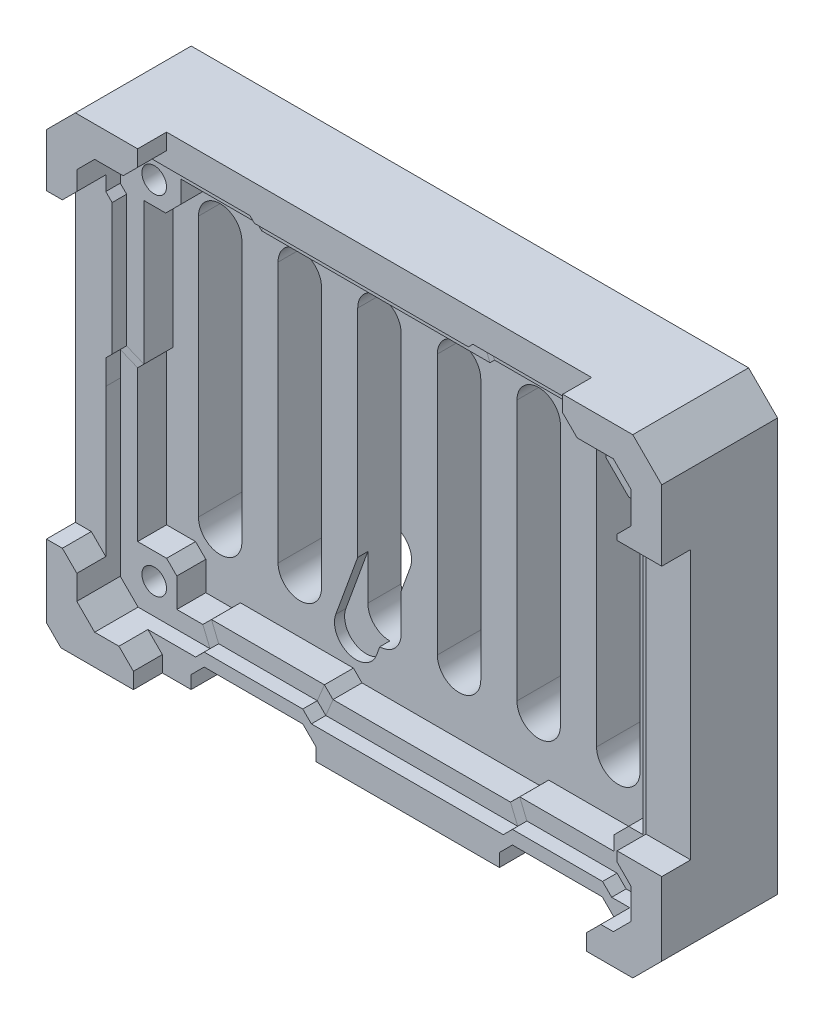
SolidWorks part; units mm, degrees
ref_plane "前视基准面" through (0, 0, 0) normal (0, 0, 1) x (1, 0, 0)
ref_plane "上视基准面" through (0, 0, 0) normal (0, 1, 0) x (1, 0, 0)
ref_plane "右视基准面" through (0, 0, 0) normal (1, 0, 0) x (0, 0, -1)
other "Configuration Table"
sketch "草图1" plane through (0, 0, 0) normal (0, 0, 1) x (1, 0, 0)
  line L1 (0, 0) -> (75, 0)
  line L2 (0, 0) -> (0, -55)
  line L3 (0, -55) -> (75, -55)
  line L4 (75, 0) -> (75, -55)
  dimension "D1" = 55
  dimension "D2" = 75
extrude "凸台-拉伸1" add sketch "草图1" along normal blind 12
sketch "草图2" plane through (0, 0, 0) normal (0, 0, -1) x (-1, 0, 0)
  circle A0 centre (-71.1669, -3.5575) radius 1.7
  circle A1 centre (-71.1669, -51.5849) radius 1.7
  circle A2 centre (-3.8888, -51.5849) radius 1.7
  circle A3 centre (-3.8888, -3.5575) radius 1.7
  dimension "D1" = 3.4
  dimension "D2" = 3.4
  dimension "D3" = 3.4
  dimension "D4" = 3.4
extrude "切除-拉伸1" cut sketch "草图2" against normal blind 12
sketch "草图3" plane through (0, 0, 0) normal (0, 0, -1) x (-1, 0, 0)
  line L1 (-73.9669, -0.7575) -> (-68.3669, -0.7575)
  line L2 (-73.9669, -0.7575) -> (-73.9669, -6.3575)
  line L3 (-73.9669, -6.3575) -> (-68.3669, -6.3575)
  line L4 (-68.3669, -0.7575) -> (-68.3669, -6.3575)
  line L5 (-73.9669, -0.7575) -> (-68.3669, -6.3575) construction
  line L6 (-73.9669, -6.3575) -> (-68.3669, -0.7575) construction
  line L11 (-6.6888, -0.7575) -> (-1.0888, -0.7575)
  line L12 (-6.6888, -0.7575) -> (-6.6888, -6.3575)
  line L13 (-6.6888, -6.3575) -> (-1.0888, -6.3575)
  line L14 (-1.0888, -0.7575) -> (-1.0888, -6.3575)
  line L15 (-6.6888, -0.7575) -> (-1.0888, -6.3575) construction
  line L16 (-6.6888, -6.3575) -> (-1.0888, -0.7575) construction
  line L17 (-73.9669, -48.7849) -> (-68.3669, -48.7849)
  line L18 (-73.9669, -48.7849) -> (-73.9669, -54.3849)
  line L19 (-73.9669, -54.3849) -> (-68.3669, -54.3849)
  line L20 (-68.3669, -48.7849) -> (-68.3669, -54.3849)
  line L21 (-73.9669, -48.7849) -> (-68.3669, -54.3849) construction
  line L22 (-73.9669, -54.3849) -> (-68.3669, -48.7849) construction
  line L23 (-6.6888, -48.7849) -> (-1.0888, -48.7849)
  line L24 (-6.6888, -48.7849) -> (-6.6888, -54.3849)
  line L25 (-6.6888, -54.3849) -> (-1.0888, -54.3849)
  line L26 (-1.0888, -48.7849) -> (-1.0888, -54.3849)
  line L27 (-6.6888, -48.7849) -> (-1.0888, -54.3849) construction
  line L28 (-6.6888, -54.3849) -> (-1.0888, -48.7849) construction
  circle A0 centre (-71.1669, -3.5575) radius 1.7 construction
  circle A1 centre (-3.8888, -3.5575) radius 1.7 construction
  circle A2 centre (-71.1669, -51.5849) radius 1.7 construction
  circle A3 centre (-3.8888, -51.5849) radius 1.7 construction
  point P0 (-71.1669, -3.5575)
  point P5 (0, 0)
  point P8 (-71.1669, -51.5849)
  point P12 (-3.8888, -3.5575)
  point P22 (-3.8888, -51.5849)
  dimension "D1" = 5.6
  dimension "D2" = 5.6
  dimension "D3" = 5.6
  dimension "D4" = 5.6
  dimension "D5" = 5.6
  dimension "D6" = 5.6
  dimension "D7" = 5.6
  dimension "D8" = 5.6
extrude "切除-拉伸2" cut sketch "草图3" along normal blind 2.5 from offset 4 offset against normal yes
sketch "草图5" plane through (0, 0, 0) normal (0, 0, -1) x (-1, 0, 0)
  line L1 (-80, 5) -> (5, 5)
  line L2 (-80, 5) -> (-80, -60)
  line L3 (-80, -60) -> (5, -60)
  line L4 (5, 5) -> (5, -60)
  line L5 (-80, 5) -> (5, -60) construction
  line L6 (-80, -60) -> (5, 5) construction
  line L10 (-75, 0) -> (0, 0) construction
  line L11 (0, 0) -> (0, -55) construction
  line L12 (-75, -55) -> (-75, 0) construction
  line L13 (-75, 0) -> (0, 0)
  line L14 (-75, 0) -> (-75, -55)
  line L15 (-75, -55) -> (0, -55)
  line L16 (0, 0) -> (0, -55)
  line L17 (0, -55) -> (-75, -55) construction
  point P0 (-37.5, -27.5)
  dimension "D1" = 65
  dimension "D2" = 85
  dimension "D3" = 5
  dimension "D4" = 5
extrude "凸台-拉伸2" add sketch "草图5" against normal up to surface (12 mm away) up to face at (2.1888, -3.5575, 12)
sketch "草图6" plane through (0, 0, 12) normal (0, 0, 1) x (1, 0, 0)
  line L56 (0.8713, -25.6658) -> (0, -26.5371)
  line L57 (0, -26.5371) -> (0, -53.0074)
  line L58 (0, -53.0074) -> (1.9926, -55)
  line L59 (1.9926, -55) -> (11.2697, -55)
  line L60 (11.2697, -55) -> (12.4616, -53.8134)
  line L61 (12.4616, -53.8134) -> (26.7436, -53.8171)
  line L62 (26.7436, -53.8171) -> (27.9265, -55)
  line L63 (27.9265, -55) -> (53.7727, -55)
  line L64 (53.7727, -55) -> (55.0435, -53.7345)
  line L65 (55.0435, -53.7345) -> (68.1524, -53.7382)
  line L66 (68.1524, -53.7382) -> (69.4142, -55)
  line L67 (69.4142, -55) -> (72.9822, -55)
  line L68 (72.9822, -55) -> (74.9747, -53.0074)
  line L69 (74.9747, -53.0074) -> (74.9747, -49.4917)
  line L70 (74.9747, -49.4917) -> (73.0283, -47.54)
  line L71 (73.0283, -47.54) -> (73.032, -7.6469)
  line L72 (73.032, -7.6469) -> (74.9747, -5.7042)
  line L73 (74.9747, -5.7042) -> (74.9747, -2.0179)
  line L74 (74.9747, -2.0179) -> (72.9822, -0.0253)
  line L75 (72.9822, -0.0253) -> (50.2451, -0.0253)
  line L76 (50.2451, -0.0253) -> (49.6148, -0.6503)
  line L77 (49.6148, -0.6503) -> (19.3949, -0.6466)
  line L78 (19.3949, -0.6466) -> (18.7736, -0.0253)
  line L79 (18.7736, -0.0253) -> (1.9926, -0.0253)
  line L80 (1.9926, -0.0253) -> (0, -2.0179)
  line L81 (0, -2.0179) -> (0, -5.9826)
  line L82 (0, -5.9826) -> (0.875, -6.8629)
  line L83 (0.875, -6.8629) -> (0.8713, -25.6658)
extrude "切除-拉伸3" cut sketch "草图6" against normal blind 2
sketch "草图7" plane through (0, 0, 10) normal (0, 0, 1) x (1, 0, 0)
  line L28 (0.875, -6.8629) -> (0.8713, -25.6658)
  line L29 (0.8713, -25.6658) -> (0, -26.5371)
  line L30 (0, -26.5371) -> (0, -53.0074)
  line L31 (0, -53.0074) -> (1.9926, -55)
  line L32 (1.9926, -55) -> (11.2697, -55)
  line L33 (11.2697, -55) -> (12.4616, -53.8134)
  line L34 (12.4616, -53.8134) -> (26.7436, -53.8171)
  line L35 (26.7436, -53.8171) -> (27.9265, -55)
  line L36 (27.9265, -55) -> (53.7727, -55)
  line L37 (53.7727, -55) -> (55.0435, -53.7345)
  line L38 (55.0435, -53.7345) -> (68.1524, -53.7382)
  line L39 (68.1524, -53.7382) -> (69.4142, -55)
  line L40 (69.4142, -55) -> (72.9822, -55)
  line L41 (72.9822, -55) -> (74.9747, -53.0074)
  line L42 (74.9747, -53.0074) -> (74.9747, -49.4917)
  line L43 (74.9747, -49.4917) -> (73.0283, -47.54)
  line L44 (73.0283, -47.54) -> (73.032, -7.6469)
  line L45 (73.032, -7.6469) -> (74.9747, -5.7042)
  line L46 (74.9747, -5.7042) -> (74.9747, -2.0179)
  line L47 (74.9747, -2.0179) -> (72.9822, -0.0253)
  line L48 (72.9822, -0.0253) -> (50.2451, -0.0253)
  line L49 (50.2451, -0.0253) -> (49.6148, -0.6503)
  line L50 (49.6148, -0.6503) -> (19.3949, -0.6466)
  line L51 (19.3949, -0.6466) -> (18.7736, -0.0253)
  line L52 (18.7736, -0.0253) -> (1.9926, -0.0253)
  line L53 (1.9926, -0.0253) -> (0, -2.0179)
  line L54 (0, -2.0179) -> (0, -5.9826)
  line L55 (0, -5.9826) -> (0.875, -6.8629)
  line L56 (0.875, -6.8629) -> (0.8713, -25.6658)
  line L57 (0.8713, -25.6658) -> (0, -26.5371)
  line L58 (0, -26.5371) -> (0, -53.0074)
  line L59 (0, -53.0074) -> (1.9926, -55)
  line L60 (1.9926, -55) -> (11.2697, -55)
  line L61 (11.2697, -55) -> (12.4616, -53.8134)
  line L62 (12.4616, -53.8134) -> (26.7436, -53.8171)
  line L63 (26.7436, -53.8171) -> (27.9265, -55)
  line L64 (27.9265, -55) -> (53.7727, -55)
  line L65 (53.7727, -55) -> (55.0435, -53.7345)
  line L66 (55.0435, -53.7345) -> (68.1524, -53.7382)
  line L67 (68.1524, -53.7382) -> (69.4142, -55)
  line L68 (69.4142, -55) -> (72.9822, -55)
  line L69 (72.9822, -55) -> (74.9747, -53.0074)
  line L70 (74.9747, -53.0074) -> (74.9747, -49.4917)
  line L71 (74.9747, -49.4917) -> (73.0283, -47.54)
  line L72 (73.0283, -47.54) -> (73.032, -7.6469)
  line L73 (73.032, -7.6469) -> (74.9747, -5.7042)
  line L74 (74.9747, -5.7042) -> (74.9747, -2.0179)
  line L75 (74.9747, -2.0179) -> (72.9822, -0.0253)
  line L76 (72.9822, -0.0253) -> (50.2451, -0.0253)
  line L77 (50.2451, -0.0253) -> (49.6148, -0.6503)
  line L78 (49.6148, -0.6503) -> (19.3949, -0.6466)
  line L79 (19.3949, -0.6466) -> (18.7736, -0.0253)
  line L80 (18.7736, -0.0253) -> (1.9926, -0.0253)
  line L81 (1.9926, -0.0253) -> (0, -2.0179)
  line L82 (0, -2.0179) -> (0, -5.9826)
  line L83 (0, -5.9826) -> (0.875, -6.8629)
  dimension "D1" = 0
sketch "草图8" plane through (47.4663, -29.6173, 16.8349) normal (0, 1, 0) x (1, 0, 0)
  line L0 (-52.4663, 4.8349) -> (32.5337, 4.8349) construction
  line L1 (-47.4663, 6.8349) -> (-48.2663, 6.8349)
  line L2 (-47.4663, 6.8349) -> (-47.4663, 4.8349)
  line L3 (-47.4663, 4.8349) -> (-48.2663, 4.8349)
  line L4 (-48.2663, 6.8349) -> (-48.2663, 4.8349)
  point P6 (-47.4663, 8.8349)
  dimension "D1" = 0.8
  dimension "D2" = 2
sweep "切除-扫描1" cut profiles "草图8" path "草图7"
sketch "草图9" plane through (0, 0, 10) normal (0, 0, 1) x (1, 0, 0)
  line L56 (0.8713, -25.6658) -> (0, -26.5371)
  line L57 (0, -26.5371) -> (0, -53.0074)
  line L58 (0, -53.0074) -> (1.9926, -55)
  line L59 (1.9926, -55) -> (11.2697, -55)
  line L60 (11.2697, -55) -> (12.4616, -53.8134)
  line L61 (12.4616, -53.8134) -> (26.7436, -53.8171)
  line L62 (26.7436, -53.8171) -> (27.9265, -55)
  line L63 (27.9265, -55) -> (53.7727, -55)
  line L64 (53.7727, -55) -> (55.0435, -53.7345)
  line L65 (55.0435, -53.7345) -> (68.1524, -53.7382)
  line L66 (68.1524, -53.7382) -> (69.4142, -55)
  line L67 (69.4142, -55) -> (72.9822, -55)
  line L68 (72.9822, -55) -> (74.9747, -53.0074)
  line L69 (74.9747, -53.0074) -> (74.9747, -49.4917)
  line L70 (74.9747, -49.4917) -> (73.0283, -47.54)
  line L71 (73.0283, -47.54) -> (73.032, -7.6469)
  line L72 (73.032, -7.6469) -> (74.9747, -5.7042)
  line L73 (74.9747, -5.7042) -> (74.9747, -2.0179)
  line L74 (74.9747, -2.0179) -> (72.9822, -0.0253)
  line L75 (72.9822, -0.0253) -> (50.2451, -0.0253)
  line L76 (50.2451, -0.0253) -> (49.6148, -0.6503)
  line L77 (49.6148, -0.6503) -> (19.3949, -0.6466)
  line L78 (19.3949, -0.6466) -> (18.7736, -0.0253)
  line L79 (18.7736, -0.0253) -> (1.9926, -0.0253)
  line L80 (1.9926, -0.0253) -> (0, -2.0179)
  line L81 (0, -2.0179) -> (0, -5.9826)
  line L82 (0, -5.9826) -> (0.875, -6.8629)
  line L83 (0.875, -6.8629) -> (0.8713, -25.6658)
extrude "切除-拉伸4" cut sketch "草图9" against normal blind 4
sketch "草图10" plane through (0, 0, 6) normal (0, 0, 1) x (1, 0, 0)
  line L28 (0.875, -6.8629) -> (0.8713, -25.6658)
  line L29 (0.8713, -25.6658) -> (0, -26.5371)
  line L30 (0, -26.5371) -> (0, -53.0074)
  line L31 (0, -53.0074) -> (1.9926, -55)
  line L32 (1.9926, -55) -> (11.2697, -55)
  line L33 (11.2697, -55) -> (12.4616, -53.8134)
  line L34 (12.4616, -53.8134) -> (26.7436, -53.8171)
  line L35 (26.7436, -53.8171) -> (27.9265, -55)
  line L36 (27.9265, -55) -> (53.7727, -55)
  line L37 (53.7727, -55) -> (55.0435, -53.7345)
  line L38 (55.0435, -53.7345) -> (68.1524, -53.7382)
  line L39 (68.1524, -53.7382) -> (69.4142, -55)
  line L40 (69.4142, -55) -> (72.9822, -55)
  line L41 (72.9822, -55) -> (74.9747, -53.0074)
  line L42 (74.9747, -53.0074) -> (74.9747, -49.4917)
  line L43 (74.9747, -49.4917) -> (73.0283, -47.54)
  line L44 (73.0283, -47.54) -> (73.032, -7.6469)
  line L45 (73.032, -7.6469) -> (74.9747, -5.7042)
  line L46 (74.9747, -5.7042) -> (74.9747, -2.0179)
  line L47 (74.9747, -2.0179) -> (72.9822, -0.0253)
  line L48 (72.9822, -0.0253) -> (50.2451, -0.0253)
  line L49 (50.2451, -0.0253) -> (49.6148, -0.6503)
  line L50 (49.6148, -0.6503) -> (19.3949, -0.6466)
  line L51 (19.3949, -0.6466) -> (18.7736, -0.0253)
  line L52 (18.7736, -0.0253) -> (1.9926, -0.0253)
  line L53 (1.9926, -0.0253) -> (0, -2.0179)
  line L54 (0, -2.0179) -> (0, -5.9826)
  line L55 (0, -5.9826) -> (0.875, -6.8629)
  line L56 (0.875, -6.8629) -> (0.8713, -25.6658)
  line L57 (0.8713, -25.6658) -> (0, -26.5371)
  line L58 (0, -26.5371) -> (0, -53.0074)
  line L59 (0, -53.0074) -> (1.9926, -55)
  line L60 (1.9926, -55) -> (11.2697, -55)
  line L61 (11.2697, -55) -> (12.4616, -53.8134)
  line L62 (12.4616, -53.8134) -> (26.7436, -53.8171)
  line L63 (26.7436, -53.8171) -> (27.9265, -55)
  line L64 (27.9265, -55) -> (53.7727, -55)
  line L65 (53.7727, -55) -> (55.0435, -53.7345)
  line L66 (55.0435, -53.7345) -> (68.1524, -53.7382)
  line L67 (68.1524, -53.7382) -> (69.4142, -55)
  line L68 (69.4142, -55) -> (72.9822, -55)
  line L69 (72.9822, -55) -> (74.9747, -53.0074)
  line L70 (74.9747, -53.0074) -> (74.9747, -49.4917)
  line L71 (74.9747, -49.4917) -> (73.0283, -47.54)
  line L72 (73.0283, -47.54) -> (73.032, -7.6469)
  line L73 (73.032, -7.6469) -> (74.9747, -5.7042)
  line L74 (74.9747, -5.7042) -> (74.9747, -2.0179)
  line L75 (74.9747, -2.0179) -> (72.9822, -0.0253)
  line L76 (72.9822, -0.0253) -> (50.2451, -0.0253)
  line L77 (50.2451, -0.0253) -> (49.6148, -0.6503)
  line L78 (49.6148, -0.6503) -> (19.3949, -0.6466)
  line L79 (19.3949, -0.6466) -> (18.7736, -0.0253)
  line L80 (18.7736, -0.0253) -> (1.9926, -0.0253)
  line L81 (1.9926, -0.0253) -> (0, -2.0179)
  line L82 (0, -2.0179) -> (0, -5.9826)
  line L83 (0, -5.9826) -> (0.875, -6.8629)
  dimension "D1" = 0
sketch "草图12" plane through (47.4663, -29.6173, 16.8349) normal (0, 1, 0) x (1, 0, 0)
  line L1 (25.5638, 6.8349) -> (23.9638, 6.8349)
  line L2 (25.5638, 6.8349) -> (25.5638, 10.8349)
  line L3 (25.5638, 10.8349) -> (23.9638, 10.8349)
  line L4 (23.9638, 6.8349) -> (23.9638, 10.8349)
  line L5 (25.562, 10.8349) -> (25.5657, 10.8349) construction
  point P4 (25.3194, 10.8162)
  point P5 (25.5159, 10.8349)
  point P6 (24.9663, 10.8134)
  point P7 (25.5595, 10.8065)
  point P8 (0, 0)
  point P10 (0, 0)
  dimension "D1" = 1.6
  dimension "D2" = 4
sweep "扫描1" add profiles "草图12" path "草图10"
sketch "草图13" plane through (0, 0, 6) normal (0, 0, 1) x (1, 0, 0)
  line L0 (32.4396, -35.2498) -> (27.7881, -48.0296) construction
  line L1 (32.0804, -36.2365) -> (32.7987, -34.2631) construction
  line L2 (27.429, -49.0163) -> (28.1472, -47.0429) construction
  line L3 (35.2586, -36.2759) -> (30.6072, -49.0557)
  line L4 (29.6205, -34.2237) -> (24.969, -47.0036)
  arc A0 (35.2586, -36.2759) -> (29.6205, -34.2237) centre (32.4396, -35.2498) ccw
  arc A1 (24.969, -47.0036) -> (30.6072, -49.0557) centre (27.7881, -48.0296) ccw
  point P6 (30.1138, -41.6397)
  dimension "D1" = 3
extrude "切除-拉伸5" cut sketch "草图13" against normal blind 1.4
sketch "草图15" plane through (0, 0, 6) normal (0, 0, 1) x (1, 0, 0)
  line L0 (1.5998, -47.986) -> (5.5998, -47.986)
  line L1 (1.5998, -52.3448) -> (1.5998, -27.1998) construction
  line L2 (5.5998, -47.986) -> (7.014, -49.4002)
  line L3 (7.014, -49.4002) -> (7.014, -53.4002)
  line L4 (10.6091, -53.4002) -> (2.6552, -53.4002) construction
  line L5 (7.014, -53.4002) -> (2.6552, -53.4002)
  line L6 (2.6552, -53.4002) -> (1.5998, -52.3448) construction
  line L7 (2.6552, -53.4002) -> (1.5998, -52.3448)
  line L8 (-0.8, -53.3388) -> (1.5998, -52.3448) construction
  line L9 (1.5998, -52.3448) -> (1.5998, -47.986)
  line L10 (71.4284, -48.1382) -> (69.4284, -48.1382)
  line L11 (7.5962, -1.6251) -> (7.5962, -4.6251)
  line L12 (2.6552, -1.6251) -> (18.1109, -1.6251) construction
  line L13 (69.4284, -48.1382) -> (67.4284, -50.1382)
  line L14 (67.4284, -50.1382) -> (67.4284, -52.1382)
  line L15 (68.8153, -52.1386) -> (54.383, -52.1345) construction
  line L16 (71.4302, -29.6173) -> (71.4284, -48.2013) construction
  line L17 (67.4284, -52.1382) -> (68.8153, -52.1386)
  line L18 (67.821, -54.5381) -> (68.8153, -52.1386) construction
  line L19 (68.8153, -52.1386) -> (70.0769, -53.4002)
  line L20 (69.0829, -55.8) -> (70.0769, -53.4002) construction
  line L21 (72.3195, -53.4002) -> (70.0769, -53.4002) construction
  line L22 (70.0769, -53.4002) -> (72.3195, -53.4002)
  line L23 (73.3136, -55.8) -> (72.3195, -53.4002) construction
  line L24 (72.3195, -53.4002) -> (73.3749, -52.3448)
  line L25 (73.3749, -52.3448) -> (72.3195, -53.4002) construction
  line L26 (73.3749, -52.3448) -> (73.3749, -50.1531)
  line L27 (71.4284, -48.2013) -> (73.3749, -50.1531) construction
  line L28 (75.7747, -49.161) -> (73.3749, -50.1531) construction
  line L29 (73.3749, -50.1531) -> (71.4284, -48.2013)
  line L30 (71.4284, -48.2013) -> (71.4284, -48.1382)
  line L31 (72.3195, -1.6251) -> (66.3195, -1.6251)
  line L32 (72.3195, -1.6251) -> (73.3749, -2.6805) construction
  line L33 (50.9039, -1.6251) -> (72.3195, -1.6251) construction
  line L34 (66.3195, -1.6251) -> (66.3195, -5.6251)
  line L35 (66.3195, -5.6251) -> (69.4321, -8.7377)
  line L36 (69.4321, -8.7377) -> (71.4321, -8.7377)
  line L37 (71.4321, -8.7377) -> (71.4323, -6.9842)
  line L38 (71.4323, -6.9842) -> (73.3035, -5.113)
  line L39 (73.3749, -5.0415) -> (71.4323, -6.9842) construction
  line L40 (73.3035, -5.113) -> (73.3749, -5.0415)
  line L41 (73.3749, -2.6805) -> (73.3749, -5.0415) construction
  line L42 (73.3749, -5.0415) -> (73.3749, -2.6805)
  line L43 (73.3749, -2.6805) -> (72.3195, -1.6251)
  line L44 (73.832, -7.9783) -> (71.4323, -6.9842) construction
  line L45 (71.4323, -6.9842) -> (71.4302, -29.6173) construction
  line L46 (7.5962, -4.6251) -> (5.4749, -6.7464)
  line L47 (5.4749, -6.7464) -> (2.4749, -6.7464)
  line L48 (2.471, -26.3286) -> (2.475, -6.2032) construction
  line L49 (2.4749, -6.7464) -> (2.475, -6.2032)
  line L50 (0.075, -7.1928) -> (2.475, -6.2032) construction
  line L51 (2.475, -6.2032) -> (1.5998, -5.3228) construction
  line L52 (2.475, -6.2032) -> (1.5998, -5.3228)
  line L53 (1.5998, -5.3228) -> (1.5998, -2.6805) construction
  line L54 (1.5998, -5.3228) -> (1.5998, -2.6805)
  line L55 (1.5998, -2.6805) -> (2.6552, -1.6251) construction
  line L56 (-0.8, -1.6865) -> (1.5998, -2.6805) construction
  line L57 (1.5998, -2.6805) -> (2.6552, -1.6251)
  line L58 (1.6612, 0.7747) -> (2.6552, -1.6251) construction
  line L59 (2.6552, -1.6251) -> (7.5962, -1.6251)
  circle A0 centre (3.8888, -3.5575) radius 1.7
  circle A1 centre (71.1669, -3.5575) radius 1.7
  circle A2 centre (71.1669, -51.5849) radius 1.7
  circle A3 centre (3.8888, -51.5849) radius 1.7
  dimension "D1" = 135
  dimension "D2" = 4
  dimension "D3" = 4
  dimension "D4" = 2
  dimension "D5" = 2
  dimension "D6" = 2
  dimension "D7" = 2
  dimension "D8" = 135
  dimension "D9" = 6
  dimension "D10" = 135
  dimension "D11" = 2
  dimension "6" = 4
  dimension "D12" = 3
  dimension "D13" = 3
  dimension "D14" = 3
  dimension "D15" = 135
extrude "凸台-拉伸3" add sketch "草图15" along normal up to surface (4 mm away) contours L9 L0 L2 L3 L5 L7 | L59 L11 L46 L47 L49 L52 L54 L57 | L43 L31 L34 L35 L36 L37 L38 L40 L42 | L30 L10 L13 L14 L17 L19 L22 L24 L26 L29 up to face at (34.5051, -0.4484, 10)
sketch "草图16" plane through (0, 0, 6) normal (0, 0, -1) x (-1, 0, 0)
  circle A0 centre (-3.8888, -51.5849) radius 1.7 construction
  circle A1 centre (-71.1669, -51.5849) radius 1.7 construction
  circle A2 centre (-71.1669, -3.5575) radius 1.7 construction
  circle A3 centre (-3.8888, -3.5575) radius 1.7 construction
  circle A4 centre (-3.8888, -51.5849) radius 1.7
  circle A5 centre (-71.1669, -51.5849) radius 1.7
  circle A6 centre (-71.1669, -3.5575) radius 1.7
  circle A7 centre (-3.8888, -3.5575) radius 1.7
extrude "切除-拉伸6" cut sketch "草图16" against normal up to surface (4 mm away) up to face at (70.599, -31.3771, 10)
sketch "草图17" plane through (0, 0, 6) normal (0, 0, 1) x (1, 0, 0)
  line L0 (9, -8.8523) -> (9, -44.8523) construction
  line L1 (12, -8.8523) -> (12, -44.8523)
  line L2 (6, -8.8523) -> (6, -44.8523)
  line L3 (-5, -60) -> (-5, 5) construction
  line L4 (20, -8.8523) -> (20, -44.8523) construction
  line L5 (23, -8.8523) -> (23, -44.8523)
  line L6 (17, -8.8523) -> (17, -44.8523)
  line L7 (31, -8.8523) -> (31, -44.8523) construction
  line L8 (34, -8.8523) -> (34, -44.8523)
  line L9 (28, -8.8523) -> (28, -44.8523)
  line L10 (42, -8.8523) -> (42, -44.8523) construction
  line L11 (45, -8.8523) -> (45, -44.8523)
  line L12 (39, -8.8523) -> (39, -44.8523)
  line L13 (53, -8.8523) -> (53, -44.8523) construction
  line L14 (56, -8.8523) -> (56, -44.8523)
  line L15 (50, -8.8523) -> (50, -44.8523)
  line L16 (64, -8.8523) -> (64, -44.8523) construction
  line L17 (67, -8.8523) -> (67, -44.8523)
  line L18 (61, -8.8523) -> (61, -44.8523)
  arc A0 (12, -8.8523) -> (6, -8.8523) centre (9, -8.8523) ccw
  arc A1 (6, -44.8523) -> (12, -44.8523) centre (9, -44.8523) ccw
  arc A2 (23, -8.8523) -> (17, -8.8523) centre (20, -8.8523) ccw
  arc A3 (17, -44.8523) -> (23, -44.8523) centre (20, -44.8523) ccw
  arc A4 (34, -8.8523) -> (28, -8.8523) centre (31, -8.8523) ccw
  arc A5 (28, -44.8523) -> (34, -44.8523) centre (31, -44.8523) ccw
  arc A6 (45, -8.8523) -> (39, -8.8523) centre (42, -8.8523) ccw
  arc A7 (39, -44.8523) -> (45, -44.8523) centre (42, -44.8523) ccw
  arc A8 (56, -8.8523) -> (50, -8.8523) centre (53, -8.8523) ccw
  arc A9 (50, -44.8523) -> (56, -44.8523) centre (53, -44.8523) ccw
  arc A10 (67, -8.8523) -> (61, -8.8523) centre (64, -8.8523) ccw
  arc A11 (61, -44.8523) -> (67, -44.8523) centre (64, -44.8523) ccw
  point P2 (9, -26.8523)
  point P13 (20, -26.8523)
  point P20 (31, -26.8523)
  point P27 (42, -26.8523)
  point P34 (53, -26.8523)
  point P41 (64, -26.8523)
  dimension "D1" = 3
  dimension "D2" = 36
  dimension "D3" = 14
  dimension "D4" = 6
extrude "切除-拉伸7" cut sketch "草图17" against normal up to surface (6 mm away) up to face at (2.1888, -3.5575, 0)
chamfer "倒角1" distance 4 angle 45 3 edges at (80, 5, 6) (80, -60, 6) (-5, 5, 6)
chamfer "倒角2" distance 2 angle 45 1 edges at (-5, -60, 6)
sketch "草图18" plane through (0, 0, 12) normal (0, 0, 1) x (1, 0, 0)
  line L0 (12.7918, -56.4) -> (9.1918, -60)
  line L1 (76, -60) -> (-3, -60) construction
  line L2 (9.1918, -60) -> (30.0121, -60)
  line L3 (30.0121, -60) -> (26.4121, -56.4)
  line L4 (26.4121, -56.4) -> (12.7918, -56.4)
  line L5 (26.4121, -54.617) -> (27.4064, -52.2175) construction
  line L6 (12.7918, -54.617) -> (26.4121, -54.617) construction
  line L7 (12.7918, -54.617) -> (12.7918, -60) construction
  line L8 (12.7918, -60) -> (26.4121, -60) construction
  line L9 (26.4121, -54.617) -> (26.4121, -60) construction
  line L10 (26.4121, -54.617) -> (12.7918, -54.6135) construction
  line L11 (55.3738, -54.5346) -> (54.383, -52.1345) construction
  line L12 (10.9918, -58.2) -> (10.9918, -60)
  line L13 (28.2121, -58.2) -> (28.2121, -60)
  line L14 (67.821, -54.5381) -> (55.3738, -54.5346) construction
  line L15 (55.3738, -54.5346) -> (67.781, -54.5346) construction
  line L16 (55.3738, -54.5346) -> (55.3738, -60) construction
  line L17 (55.3738, -60) -> (67.781, -60) construction
  line L18 (67.781, -54.5346) -> (67.781, -60) construction
  line L19 (55.3738, -56.4) -> (53.5738, -58.2)
  line L20 (53.5738, -58.2) -> (53.5738, -60)
  line L21 (53.5738, -60) -> (69.581, -60)
  line L22 (69.581, -60) -> (69.581, -58.2)
  line L23 (69.581, -58.2) -> (67.781, -56.4)
  line L24 (67.781, -56.4) -> (55.3738, -56.4)
  line M40 (-3, -60) -> (76, -60)
  dimension "D1" = 45
  dimension "D2" = 45
  dimension "D3" = 3.6
  dimension "D4" = 13.6203
  dimension "D5" = 12.4071
  dimension "D6" = 135
  dimension "D7" = 135
extrude "切除-拉伸8" cut sketch "草图18" against normal blind 4 contours L13 L3 L4 L0 L12 L2 | L23 L24 L19 L20 L22 M40 region at (19.602, -58.2662, 12) region at (61.5774, -58.2715, 12)
sketch "草图20" plane through (0, 0, 12) normal (0, 0, 1) x (1, 0, 0)
  line L0 (0.0714, -25.3343) -> (2.471, -26.3286) construction
  line L1 (2.471, -26.3286) -> (2.4749, -6.7464) construction
  line L2 (2.4749, -6.7464) -> (5.4749, -6.7464) construction
  line L3 (5.4749, -6.7464) -> (7.5962, -4.6251) construction
  line L4 (7.5962, -4.6251) -> (7.5962, -1.6251) construction
  line L5 (7.5962, -1.6251) -> (18.1109, -1.6251) construction
  line L6 (18.1109, -1.6251) -> (19.1049, 0.7747) construction
  line L7 (19.1049, 0.7747) -> (1.6612, 0.7747) construction
  line L8 (1.6612, 0.7747) -> (-0.8, -1.6865) construction
  line L9 (-0.8, -1.6865) -> (-0.8, -6.3126) construction
  line L10 (-0.8, -6.3126) -> (0.075, -7.1928) construction
  line L11 (0.075, -7.1928) -> (0.0714, -25.3343) construction
  line L12 (67.821, -54.5381) -> (69.0829, -55.8) construction
  line L13 (69.0829, -55.8) -> (73.3136, -55.8) construction
  line L14 (73.3136, -55.8) -> (75.7747, -53.3388) construction
  line L15 (75.7747, -53.3388) -> (75.7747, -49.161) construction
  line L16 (75.7747, -49.161) -> (73.8283, -47.2093) construction
  line L17 (73.8283, -47.2093) -> (73.832, -7.9783) construction
  line L18 (73.832, -7.9783) -> (75.7747, -6.0355) construction
  line L19 (75.7747, -6.0355) -> (75.7747, -1.6865) construction
  line L20 (75.7747, -1.6865) -> (73.3136, 0.7747) construction
  line L21 (73.3136, 0.7747) -> (49.9157, 0.7747) construction
  line L22 (49.9157, 0.7747) -> (50.9039, -1.6251) construction
  line L23 (50.9039, -1.6251) -> (66.3195, -1.6251) construction
  line L24 (66.3195, -1.6251) -> (66.3195, -5.6251) construction
  line L25 (66.3195, -5.6251) -> (69.4321, -8.7377) construction
  line L26 (69.4321, -8.7377) -> (71.4321, -8.7377) construction
  line L27 (71.4321, -8.7377) -> (71.4302, -29.6173) construction
  line L28 (71.4302, -29.6173) -> (71.4284, -48.1382) construction
  line L29 (71.4284, -48.1382) -> (69.4284, -48.1382) construction
  line L30 (69.4284, -48.1382) -> (67.4284, -50.1382) construction
  line L31 (67.4284, -50.1382) -> (67.4284, -52.1382) construction
  line L32 (67.4284, -52.1382) -> (54.383, -52.1345) construction
  line L33 (54.383, -52.1345) -> (55.3738, -54.5346) construction
  line L34 (55.3738, -54.5346) -> (67.821, -54.5381) construction
  line L35 (-0.8, -29.6173) -> (-0.8, -53.3388) construction
  line L36 (-0.8, -53.3388) -> (1.6612, -55.8) construction
  line L37 (1.6612, -55.8) -> (11.6, -55.8) construction
  line L38 (11.6, -55.8) -> (10.6091, -53.4002) construction
  line L39 (10.6091, -53.4002) -> (7.014, -53.4002) construction
  line L40 (7.014, -53.4002) -> (7.014, -49.4002) construction
  line L41 (7.014, -49.4002) -> (5.5998, -47.986) construction
  line L42 (5.5998, -47.986) -> (1.5998, -47.986) construction
  line L43 (1.5998, -47.986) -> (1.5998, -27.1998) construction
  line L44 (1.5998, -27.1998) -> (-0.8, -26.2057) construction
  line L45 (-0.8, -26.2057) -> (-0.8, -29.6173) construction
  line L46 (0.0714, -25.3343) -> (2.471, -26.3286)
  line L47 (2.471, -26.3286) -> (2.4749, -6.7464)
  line L48 (2.4749, -6.7464) -> (5.4749, -6.7464)
  line L49 (5.4749, -6.7464) -> (7.5962, -4.6251)
  line L50 (7.5962, -4.6251) -> (7.5962, -1.6251)
  line L51 (7.5962, -1.6251) -> (18.1109, -1.6251)
  line L52 (18.1109, -1.6251) -> (19.1049, 0.7747)
  line L53 (19.1049, 0.7747) -> (1.6612, 0.7747)
  line L54 (1.6612, 0.7747) -> (-0.8, -1.6865)
  line L55 (-0.8, -1.6865) -> (-0.8, -6.3126)
  line L56 (-0.8, -6.3126) -> (0.075, -7.1928)
  line L57 (0.075, -7.1928) -> (0.0714, -25.3343)
  line L58 (67.821, -54.5381) -> (69.0829, -55.8)
  line L59 (69.0829, -55.8) -> (73.3136, -55.8)
  line L60 (73.3136, -55.8) -> (75.7747, -53.3388)
  line L61 (75.7747, -53.3388) -> (75.7747, -49.161)
  line L62 (75.7747, -49.161) -> (73.8283, -47.2093)
  line L63 (73.8283, -47.2093) -> (73.832, -7.9783)
  line L64 (73.832, -7.9783) -> (75.7747, -6.0355)
  line L65 (75.7747, -6.0355) -> (75.7747, -1.6865)
  line L66 (75.7747, -1.6865) -> (73.3136, 0.7747)
  line L67 (73.3136, 0.7747) -> (49.9157, 0.7747)
  line L68 (49.9157, 0.7747) -> (50.9039, -1.6251)
  line L69 (50.9039, -1.6251) -> (66.3195, -1.6251)
  line L70 (66.3195, -1.6251) -> (66.3195, -5.6251)
  line L71 (66.3195, -5.6251) -> (69.4321, -8.7377)
  line L72 (69.4321, -8.7377) -> (71.4321, -8.7377)
  line L73 (71.4321, -8.7377) -> (71.4302, -29.6173)
  line L74 (71.4302, -29.6173) -> (71.4284, -48.1382)
  line L75 (71.4284, -48.1382) -> (69.4284, -48.1382)
  line L76 (69.4284, -48.1382) -> (67.4284, -50.1382)
  line L77 (67.4284, -50.1382) -> (67.4284, -52.1382)
  line L78 (67.4284, -52.1382) -> (54.383, -52.1345)
  line L79 (54.383, -52.1345) -> (55.3738, -54.5346)
  line L80 (55.3738, -54.5346) -> (67.821, -54.5381)
  line L81 (-0.8, -29.6173) -> (-0.8, -53.3388)
  line L82 (-0.8, -53.3388) -> (1.6612, -55.8)
  line L83 (1.6612, -55.8) -> (11.6, -55.8)
  line L84 (11.6, -55.8) -> (10.6091, -53.4002)
  line L85 (10.6091, -53.4002) -> (7.014, -53.4002)
  line L86 (7.014, -53.4002) -> (7.014, -49.4002)
  line L87 (7.014, -49.4002) -> (5.5998, -47.986)
  line L88 (5.5998, -47.986) -> (1.5998, -47.986)
  line L89 (1.5998, -47.986) -> (1.5998, -27.1998)
  line L90 (1.5998, -27.1998) -> (-0.8, -26.2057)
  line L91 (-0.8, -26.2057) -> (-0.8, -29.6173)
  line L92 (-0.8, -6.3126) -> (-5, -6.3126)
  line L93 (7.5962, -1.6251) -> (7.5962, 5)
  line L94 (66.3195, -1.6251) -> (66.3195, 5)
  line L95 (71.4321, -8.7377) -> (80, -8.7377)
  line L96 (73.8285, -45.8698) -> (80, -45.8698)
  line L97 (69.581, -58.2) -> (69.581, -55.8)
  line L98 (7.014, -53.4002) -> (7.014, -60)
  line L99 (1.5998, -47.986) -> (-5, -47.986)
  line L112 (26.4121, -56.4) -> (28.2121, -58.2)
  line L113 (28.2121, -58.2) -> (28.2121, -60)
  line L114 (28.2121, -60) -> (53.5738, -60)
  line L115 (53.5738, -60) -> (53.5738, -58.2)
  line L116 (53.5738, -58.2) -> (55.3738, -56.4)
  line L117 (55.3738, -56.4) -> (67.781, -56.4)
  line L118 (67.781, -56.4) -> (69.581, -58.2)
  line L119 (69.581, -58.2) -> (69.581, -60)
  line L120 (69.581, -60) -> (76, -60)
  line L121 (76, -60) -> (80, -56)
  line L122 (80, -56) -> (80, 1)
  line L123 (80, 1) -> (76, 5)
  line L124 (76, 5) -> (-1, 5)
  line L125 (-1, 5) -> (-5, 1)
  line L126 (-5, 1) -> (-5, -58)
  line L127 (-5, -58) -> (-3, -60)
  line L128 (-3, -60) -> (10.9918, -60)
  line L129 (10.9918, -60) -> (10.9918, -58.2)
  line L130 (10.9918, -58.2) -> (12.7918, -56.4)
  line L131 (12.7918, -56.4) -> (26.4121, -56.4)
  line L132 (26.4121, -56.4) -> (28.2121, -58.2)
  line L133 (28.2121, -58.2) -> (28.2121, -60)
  line L134 (28.2121, -60) -> (53.5738, -60)
  line L135 (53.5738, -60) -> (53.5738, -58.2)
  line L136 (53.5738, -58.2) -> (55.3738, -56.4)
  line L137 (55.3738, -56.4) -> (67.781, -56.4)
  line L138 (67.781, -56.4) -> (69.581, -58.2)
  line L139 (69.581, -58.2) -> (69.581, -60)
  line L140 (69.581, -60) -> (76, -60)
  line L141 (76, -60) -> (80, -56)
  line L142 (80, -56) -> (80, 1)
  line L143 (80, 1) -> (76, 5)
  line L144 (76, 5) -> (-1, 5)
  line L145 (-1, 5) -> (-5, 1)
  line L146 (-5, 1) -> (-5, -58)
  line L147 (-5, -58) -> (-3, -60)
  line L148 (-3, -60) -> (10.9918, -60)
  line L149 (10.9918, -60) -> (10.9918, -58.2)
  line L150 (10.9918, -58.2) -> (12.7918, -56.4)
  line L151 (12.7918, -56.4) -> (26.4121, -56.4)
  line M57 (73.8283, -47.2093) -> (75.7747, -49.161)
  line M58 (75.7747, -49.161) -> (75.7747, -53.3388)
  line M59 (75.7747, -53.3388) -> (73.3136, -55.8)
  line M60 (73.3136, -55.8) -> (69.0829, -55.8)
  line M69 (1.6612, -55.8) -> (-0.8, -53.3388)
  line M70 (-0.8, -53.3388) -> (-0.8, -29.6173)
  line M75 (-0.8, -6.3126) -> (-0.8, -1.6865)
  line M76 (-0.8, -1.6865) -> (1.6612, 0.7747)
  line M77 (1.6612, 0.7747) -> (19.1049, 0.7747)
  line M82 (73.3136, 0.7747) -> (75.7747, -1.6865)
  line M83 (75.7747, -1.6865) -> (75.7747, -6.0355)
  line M84 (75.7747, -6.0355) -> (73.832, -7.9783)
  line M85 (73.832, -7.9783) -> (73.8283, -47.2093)
  line M93 (69.581, -58.2) -> (69.581, -60)
  line M94 (69.581, -60) -> (76, -60)
  line M95 (76, -60) -> (80, -56)
  line M96 (80, -56) -> (80, 1)
  line M97 (80, 1) -> (76, 5)
  line M98 (76, 5) -> (-1, 5)
  line M99 (-1, 5) -> (-5, 1)
  line M100 (-5, 1) -> (-5, -58)
  line M101 (-5, -58) -> (-3, -60)
  line M102 (-3, -60) -> (10.9918, -60)
  dimension "D1" = 0
extrude "凸台-拉伸4" add sketch "草图20" along normal blind 4 contours L99 L98 L83 M70 M100 M101 M102 M69 | L93 L92 M77 M98 M99 M100 M75 M76 | L95 L94 L67 M85 M96 M97 M98 M82 M83 M84 | L97 M93 M94 M95 M96 M57 M58 M59 M60 region at (0.1559, 0.5355, 12) region at (-0.4227, -55.4227, 12) region at (74.7941, -0.5059, 12) region at (75.9645, -53.6761, 12)
chamfer "倒角4" distance 2 angle 45 6 edges at (69.581, -55.8, 14) (66.3195, 0.7747, 14) (7.5962, 0.7747, 14) (-0.8, -6.3126, 14) (7.014, -55.8, 14) (-0.8, -47.986, 14)
